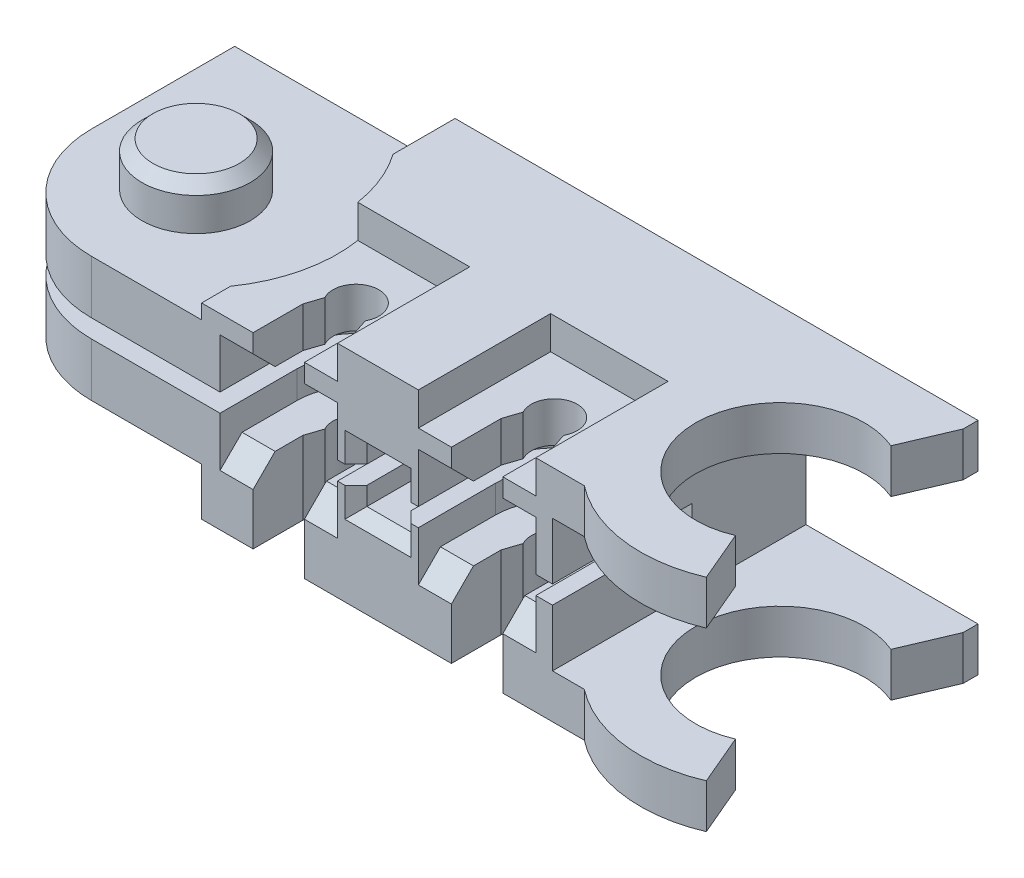
SolidWorks part; units mm, degrees
ref_plane "Front Plane" through (0, 0, 0) normal (0, 0, 1) x (1, 0, 0)
ref_plane "Top Plane" through (0, 0, 0) normal (0, 1, 0) x (1, 0, 0)
ref_plane "Right Plane" through (0, 0, 0) normal (1, 0, 0) x (0, 0, -1)
sketch "Sketch1" plane through (0, 0, 0) normal (0, 0, 1) x (1, 0, 0)
  line L0 (0, 0) -> (-17.5, 0) construction
  line L5 (-17.5, 0) -> (-35.5, 0) construction
  line L6 (-35.5, 0) -> (-53, 0) construction
  line L7 (-53, -5.67) -> (-45.5, -5.67) construction
  line L8 (-53, -10) -> (0, -10) construction
  line L9 (-53, -10) -> (-53, 10) construction
  line L10 (-53, 10) -> (0, 10) construction
  line L11 (0, -10) -> (0, 10) construction
  line L12 (-53, -10) -> (0, 10) construction
  line L13 (-53, 10) -> (0, -10) construction
  line L14 (-42.5, -10) -> (-42.5, -5.67)
  line L15 (-42.5, -5.67) -> (-53, -5.67)
  line L16 (-42.5, 10) -> (-42.5, 5.67)
  line L17 (-42.5, 5.67) -> (-53, 5.67)
  line L18 (-53, 5.67) -> (-62.5, 5.67)
  line L19 (-62.5, 5.67) -> (-62.5, -5.67)
  line L20 (-62.5, -5.67) -> (-53, -5.67)
  line L21 (-42.5, 10) -> (0, 10) construction
  line L22 (-42.5, -10) -> (0, -10)
  line L23 (0, 10) -> (3, 10)
  line L24 (3, 10) -> (3, 6)
  line L25 (3, 6) -> (0, 6)
  line L26 (0, -10) -> (3, -10)
  line L27 (3, -10) -> (3, -6)
  line L28 (3, -6) -> (0, -6)
  line L29 (0, 6) -> (0, -6) construction
  line L30 (0, 6) -> (-10.66, 6)
  line L31 (-10.66, 6) -> (-10.66, -6)
  line L32 (-10.66, -6) -> (0, -6)
  line L33 (-7.5, 0) -> (0, 0) construction
  line L34 (-7.5, 0) -> (-10.66, 0) construction
  line L35 (-42.5, 10) -> (0, 10)
  line L36 (0, 0) -> (3, 0) construction
  line L37 (3, 0) -> (3, 6) construction
  line L38 (-45.5, -5.67) -> (-42.5, -5.67) construction
  point P2 (-26.5, 0)
  dimension "D2" = 17.5
  dimension "D3" = 18
  dimension "D4" = 17.5
  dimension "D6" = 20
  dimension "D7" = 4.33
  dimension "D8" = 4
  dimension "D1" = 7.5
  dimension "D9" = 3
  dimension "D5" = 7.5
  dimension "D12" = 3
  dimension "D10" = 20
  dimension "D11" = 10.66
sketch "Sketch16" plane through (0, 0, 0) normal (0, 0, 1) x (1, 0, 0)
  line L18 (-42.5, -10) -> (0, -10)
  line L19 (0, -10) -> (3, -10)
  line L20 (3, -10) -> (3, -6)
  line L21 (3, -6) -> (0, -6)
  line L22 (0, -6) -> (-10.66, -6)
  line L23 (-10.66, -6) -> (-10.66, 6)
  line L24 (-10.66, 6) -> (0, 6)
  line L25 (0, 6) -> (3, 6)
  line L26 (3, 6) -> (3, 10)
  line L27 (3, 10) -> (0, 10)
  line L28 (0, 10) -> (-42.5, 10)
  line L29 (-42.5, 10) -> (-42.5, 5.67)
  line L30 (-42.5, 5.67) -> (-53, 5.67)
  line L31 (-53, 5.67) -> (-62.5, 5.67)
  line L32 (-62.5, 5.67) -> (-62.5, -5.67)
  line L33 (-62.5, -5.67) -> (-53, -5.67)
  line L34 (-53, -5.67) -> (-42.5, -5.67)
  line L35 (-42.5, -5.67) -> (-42.5, -10)
  line L36 (-42.5, -10) -> (0, -10)
  line L37 (0, -10) -> (3, -10)
  line L38 (3, -10) -> (3, -6)
  line L39 (3, -6) -> (0, -6)
  line L40 (0, -6) -> (-10.66, -6)
  line L41 (-10.66, -6) -> (-10.66, 6)
  line L42 (-10.66, 6) -> (0, 6)
  line L43 (0, 6) -> (3, 6)
  line L44 (3, 6) -> (3, 10)
  line L45 (3, 10) -> (0, 10)
  line L46 (0, 10) -> (-42.5, 10)
  line L47 (-42.5, 10) -> (-42.5, 5.67)
  line L48 (-42.5, 5.67) -> (-53, 5.67)
  line L49 (-53, 5.67) -> (-62.5, 5.67)
  line L50 (-62.5, 5.67) -> (-62.5, -5.67)
  line L51 (-62.5, -5.67) -> (-53, -5.67)
  line L52 (-53, -5.67) -> (-42.5, -5.67)
  line L53 (-42.5, -5.67) -> (-42.5, -10)
  dimension "D1" = 0
extrude "Boss-Extrude7" add sketch "Sketch16" along normal blind 20
sketch "Sketch2" plane through (0, -5.67, 0) normal (0, -1, 0) x (1, 0, 0)
  line L0 (-53, 0) -> (0, 0) construction
  line L1 (-53, 0) -> (0, 0) construction
  line L2 (-53, 0) -> (-53, 20) construction
  line L4 (-62.5, 20) -> (-42.5, 20) construction
  circle A0 centre (-53, 10) radius 4.9175
  dimension "D1" = 9.835
extrude "Boss-Extrude2" add sketch "Sketch2" along normal blind 4
sketch "Sketch3" plane through (0, -10, 0) normal (0, -1, 0) x (1, 0, 0)
  line L0 (0, 0) -> (0, 20) construction
  line L2 (-42.5, 20) -> (3, 20) construction
  circle A0 centre (0, 10) radius 7.665
  dimension "D1" = 15.33
extrude "Cut-Extrude1" cut sketch "Sketch3" against normal up to surface (20 mm away) up to face at (-19.75, 10, 10)
mirror "Mirror1" about plane through (0, 0, 0) normal (0, 1, 0) of "Boss-Extrude2"
sketch "Sketch4" plane through (0, 0, 20) normal (0, 0, 1) x (1, 0, 0)
  line L0 (0, -10) -> (0, 10) construction
  line L1 (0, -10) -> (0, 10) construction
  line L2 (0, 0) -> (-26.5, 0) construction
  line L3 (-17.5, 0) -> (-35.5, 0) construction
  line L4 (-28.5, 2.5) -> (-24.5, 2.5)
  line L5 (-28.5, -2.5) -> (-24.5, -2.5) construction
  line L6 (-28.5, -2.5) -> (-28.5, 2.5)
  line L7 (-28.5, 2.5) -> (-24.5, 2.5) construction
  line L8 (-24.5, -2.5) -> (-24.5, 2.5) construction
  line L9 (-28.5, -2.5) -> (-24.5, 2.5) construction
  line L10 (-28.5, 2.5) -> (-24.5, -2.5) construction
  line L11 (-28.5, -2.5) -> (-24.5, -2.5)
  line L12 (-24.5, 2.5) -> (-24.5, -2.5)
  dimension "D3" = 26.5
extrude "Cut-Extrude2" cut sketch "Sketch4" against normal blind 10
sketch "Sketch10" plane through (0, -10, 0) normal (0, -1, 0) x (1, 0, 0)
  line L0 (3, 17.0535) -> (4.9569, 21.6547)
  line L1 (4.9569, -1.6547) -> (3, 2.9465)
  arc A1 (3, 17.0535) -> (3, 2.9465) centre (0, 10) ccw
  arc A2 (4.9569, 21.6547) -> (4.9569, -1.6547) centre (0, 10) ccw
  arc A3 (3, 17.0535) -> (3, 2.9465) centre (0, 10) ccw construction
  dimension "D1" = 5
  dimension "D2" = 7.665
extrude "Boss-Extrude4" add sketch "Sketch10" against normal up to surface (4 mm away) up to face at (-3.3308, -6, 10)
sketch "Sketch11" plane through (0, 10, 0) normal (0, 1, 0) x (1, 0, 0)
  line L6 (4.9569, -21.6547) -> (3, -17.0535)
  line L8 (3, -2.9465) -> (4.9569, 1.6547)
  line L17 (-7.7719, 0) -> (-10.66, 0)
  line L19 (-10.66, 0) -> (-10.66, -20)
  line L20 (-10.66, -20) -> (-7.7719, -20)
  line L21 (4.9569, -21.6547) -> (3, -17.0535)
  line L22 (3, -2.9465) -> (4.9569, 1.6547)
  line L23 (-7.7719, 0) -> (-10.66, 0)
  line L24 (-10.66, 0) -> (-10.66, -20)
  line L25 (-10.66, -20) -> (-7.7719, -20)
  arc A11 (3, -2.9465) -> (3, -17.0535) centre (0, -10) ccw
  arc A12 (4.9569, 1.6547) -> (-7.7719, 0) centre (0, -10) ccw
  arc A13 (-7.7719, -20) -> (4.9569, -21.6547) centre (0, -10) ccw
  arc A14 (3, -2.9465) -> (3, -17.0535) centre (0, -10) ccw
  arc A15 (4.9569, 1.6547) -> (-7.7719, 0) centre (0, -10) ccw
  arc A16 (-7.7719, -20) -> (4.9569, -21.6547) centre (0, -10) ccw
  dimension "D1" = 0
extrude "Boss-Extrude5" add sketch "Sketch11" against normal up to surface (4 mm away) up to face at (-3.3308, 6, 10)
sketch "Sketch25" plane through (0, -10, 0) normal (0, -1, 0) x (1, 0, 0)
  circle A0 centre (-53, 10) radius 12.83
  circle A1 centre (-53, 10) radius 4.9175 construction
  circle A2 centre (-53, 10) radius 4.9175
  dimension "D1" = 25.66
extrude "Cut-Extrude9" cut sketch "Sketch25" against normal up to surface (4.33 mm away) up to face at (-57.9175, -5.67, 10)
sketch "Sketch26" plane through (0, 10, 0) normal (0, 1, 0) x (1, 0, 0)
  line L0 (-42.5, -2.6272) -> (-42.5, -17.3728)
  arc A0 (-42.5, -17.3728) -> (-42.5, -2.6272) centre (-53, -10) ccw construction
  arc A1 (-42.5, -17.3728) -> (-42.5, -2.6272) centre (-53, -10) ccw
extrude "Cut-Extrude10" cut sketch "Sketch26" against normal up to surface (4.33 mm away) up to face at (-48.0825, 5.67, 10)
sketch "Sketch13" plane through (0, -10, 0) normal (0, -1, 0) x (1, 0, 0)
  line L0 (-35.5, 0) -> (-35.5, 20) construction
  line L3 (-17.5, 0) -> (-17.5, 20) construction
  line L5 (-35.5, 13) -> (-17.5, 13) construction
  line L6 (-35.5, 8) -> (-17.5, 8) construction
  line L7 (-37.335, 13.9847) -> (-33.665, 13.9847) construction
  line L8 (-37.83, 15.4847) -> (-33.17, 15.4847) construction
  line L9 (-37.83, 15.4847) -> (-37.83, 20)
  line L10 (-37.83, 20) -> (-33.17, 20)
  line L11 (-33.17, 15.4847) -> (-33.17, 20)
  line L12 (-37.83, 15.4847) -> (-33.17, 20) construction
  line L13 (-37.83, 20) -> (-33.17, 15.4847) construction
  line L14 (-19.83, 15.4847) -> (-15.17, 15.4847) construction
  line L15 (-19.83, 15.4847) -> (-19.83, 20)
  line L16 (-19.83, 20) -> (-15.17, 20)
  line L17 (-15.17, 15.4847) -> (-15.17, 20)
  line L18 (-19.83, 15.4847) -> (-15.17, 20) construction
  line L19 (-19.83, 20) -> (-15.17, 15.4847) construction
  line L20 (-19.335, 13.9847) -> (-15.665, 13.9847) construction
  line L21 (-37.83, 15.4847) -> (-37.335, 13.9847)
  line L22 (-33.665, 13.9847) -> (-33.17, 15.4847)
  line L23 (-19.83, 15.4847) -> (-19.335, 13.9847)
  line L24 (-15.665, 13.9847) -> (-15.17, 15.4847)
  line L25 (-42.5, 20) -> (-7.7719, 20) construction
  line L26 (-42.5, 0) -> (-7.7719, 0) construction
  line L29 (-42.5, 0) -> (0, 0) construction
  line L30 (-17.5, 18) -> (-17.5, 20) construction
  circle A0 centre (-35.5, 13) radius 2.0825 construction
  circle A1 centre (-17.5, 13) radius 2.0825 construction
  circle A2 centre (-35.5, 13) radius 5 construction
  circle A3 centre (-17.5, 13) radius 5 construction
  arc A4 (-37.335, 13.9847) -> (-33.665, 13.9847) centre (-35.5, 13) ccw
  arc A5 (-19.335, 13.9847) -> (-15.665, 13.9847) centre (-17.5, 13) ccw
  point P11 (-35.5, 0)
  point P13 (-17.5, 0)
  point P22 (-35.5, 17.7423)
  point P27 (-17.5, 17.7423)
  point P46 (-17.5, 0)
  point P47 (-35.5, 0)
  dimension "D1" = 4.165
  dimension "D2" = 10
  dimension "D4" = 4.66
  dimension "D5" = 3.67
  dimension "D6" = 1.5
extrude "Cut-Extrude5" cut sketch "Sketch13" against normal through all
sketch "Sketch17" plane through (0, 0, 20) normal (0, 0, 1) x (1, 0, 0)
  line L1 (-40.83, -3.33) -> (-30.17, -3.33)
  line L2 (-40.83, -3.33) -> (-40.83, 3.33)
  line L3 (-40.83, 3.33) -> (-30.17, 3.33)
  line L4 (-30.17, -3.33) -> (-30.17, 3.33)
  line L5 (-40.83, -3.33) -> (-30.17, 3.33) construction
  line L6 (-40.83, 3.33) -> (-30.17, -3.33) construction
  line L7 (-22.83, -3.33) -> (-12.17, -3.33)
  line L8 (-22.83, -3.33) -> (-22.83, 3.33)
  line L9 (-22.83, 3.33) -> (-12.17, 3.33)
  line L10 (-12.17, -3.33) -> (-12.17, 3.33)
  line L11 (-22.83, -3.33) -> (-12.17, 3.33) construction
  line L12 (-22.83, 3.33) -> (-12.17, -3.33) construction
  point P0 (-35.5, 0)
  point P6 (-17.5, 0)
  dimension "D1" = 10.66
  dimension "D2" = 6.66
extrude "Cut-Extrude6" cut sketch "Sketch17" against normal blind 7
ref_axis "Axis1" through (-17.5, 10, 13) along (0, -1, 0)
ref_axis "Axis2" through (-35.5, 10, 13) along (0, -1, 0)
sketch "Sketch18" plane through (0, 0, 13) normal (0, 0, 1) x (1, 0, 0)
  line L4 (-37.5825, 3.33) -> (-40.83, 3.33)
  line L5 (-40.83, 3.33) -> (-40.83, -3.33)
  line L6 (-40.83, -3.33) -> (-37.5825, -3.33)
  line L7 (-37.5825, -3.33) -> (-37.5825, 3.33)
  line L8 (-37.5825, 3.33) -> (-40.83, 3.33)
  line L9 (-40.83, 3.33) -> (-40.83, -3.33)
  line L10 (-40.83, -3.33) -> (-37.5825, -3.33)
  line L12 (-37.5825, -3.33) -> (-37.5825, 3.33)
  dimension "D1" = 0
revolve "Cut-Revolve1" cut sketch "Sketch18" angle 360 about axis through (-35.5, 10, 13) along (0, -1, 0)
sketch "Sketch19" plane through (0, 0, 13) normal (0, 0, 1) x (1, 0, 0)
  line L4 (-19.5825, 3.33) -> (-22.83, 3.33)
  line L5 (-22.83, 3.33) -> (-22.83, -3.33)
  line L6 (-22.83, -3.33) -> (-19.5825, -3.33)
  line L7 (-19.5825, -3.33) -> (-19.5825, 3.33)
  line L8 (-19.5825, 3.33) -> (-22.83, 3.33)
  line L9 (-22.83, 3.33) -> (-22.83, -3.33)
  line L10 (-22.83, -3.33) -> (-19.5825, -3.33)
  line L12 (-19.5825, -3.33) -> (-19.5825, 3.33)
  dimension "D1" = 0
revolve "Cut-Revolve2" cut sketch "Sketch19" angle 360 about axis through (-17.5, 10, 13) along (0, -1, 0)
sketch "Sketch20" plane through (0, 0, 20) normal (0, 0, 1) x (1, 0, 0)
  line L0 (-62.5, 5.67) -> (-62.5, -5.67) construction
  line L1 (-62.5, 0.83) -> (-10.66, 0.83)
  line L2 (-62.5, 0.83) -> (-62.5, -0.83)
  line L3 (-62.5, -0.83) -> (-10.66, -0.83)
  line L4 (-10.66, 0.83) -> (-10.66, -0.83)
  line L5 (-10.66, 6) -> (-10.66, -6) construction
  dimension "D1" = 1.66
extrude "Cut-Extrude7" cut sketch "Sketch20" against normal blind 12.66
chamfer "Chamfer2" distance 1 angle 45 1 edges at (-48.0825, -9.67, 10)
chamfer "Chamfer3" distance 1 angle 45 1 edges at (-48.0825, 9.67, 10)
chamfer "Chamfer4" distance 2 angle 45 8 edges at (-21.33, 3.33, 20) (-21.33, -3.33, 20) (-13.67, -3.33, 20) (-13.67, 3.33, 20) (-39.33, -3.33, 20) (-39.33, 3.33, 20) (-31.67, -3.33, 20) (-31.67, 3.33, 20)
fillet "Fillet1" radius 10 3 edges at (-62.5, 0, 0) (-62.5, 3.25, 20) (-62.5, -3.25, 20)
ref_plane "Plane1" through (0, 0, -3) normal (0, 0, -1) x (-1, 0, 0)
sketch "Sketch22" plane through (0, 0, -3) normal (0, 0, -1) x (-1, 0, 0)
  line L0 (62.5, 5.67) -> (52.5, 5.67) construction
  line L1 (52.5, -5.67) -> (62.5, -5.67) construction
  line L2 (62.5, -5.67) -> (62.5, -0.83) construction
  line L3 (62.5, -0.83) -> (62.1397, -0.83) construction
  line L4 (62.1397, -0.83) -> (62.1397, 0.83) construction
  line L5 (62.1397, 0.83) -> (62.5, 0.83) construction
  line L6 (62.5, 0.83) -> (62.5, 5.67) construction
  line L7 (-4.9569, 6) -> (7.7719, 6) construction
  line L8 (7.7719, 10) -> (-4.9569, 10) construction
  line L9 (-4.9569, 10) -> (-4.9569, 6) construction
  line L10 (7.7719, -6) -> (-4.9569, -6) construction
  line L11 (-4.9569, -6) -> (-4.9569, -10) construction
  line L12 (-4.9569, -10) -> (7.7719, -10) construction
  line L13 (42.5, -5.67) -> (52.5, -5.67) construction
  line L14 (52.5, 5.67) -> (42.5, 5.67) construction
  line L15 (42.5, 5.67) -> (42.5, 10) construction
  line L16 (42.5, 10) -> (7.7719, 10) construction
  line L17 (7.7719, 6) -> (10.66, 6) construction
  line L18 (10.66, 6) -> (10.66, -6) construction
  line L19 (10.66, -6) -> (7.7719, -6) construction
  line L20 (7.7719, -10) -> (42.5, -10) construction
  line L21 (42.5, -10) -> (42.5, -5.67) construction
  line L22 (62.5, 5.67) -> (52.5, 5.67)
  line L23 (52.5, -5.67) -> (62.5, -5.67)
  line L24 (62.5, -5.67) -> (62.5, -0.83)
  line L25 (62.5, -0.83) -> (62.1397, -0.83)
  line L26 (62.1397, -0.83) -> (62.1397, 0.83)
  line L27 (62.1397, 0.83) -> (62.5, 0.83)
  line L28 (62.5, 0.83) -> (62.5, 5.67)
  line L29 (-4.9569, 6) -> (7.7719, 6)
  line L30 (7.7719, 10) -> (-4.9569, 10)
  line L31 (-4.9569, 10) -> (-4.9569, 6)
  line L32 (7.7719, -6) -> (-4.9569, -6)
  line L33 (-4.9569, -6) -> (-4.9569, -10)
  line L34 (-4.9569, -10) -> (7.7719, -10)
  line L35 (42.5, -5.67) -> (52.5, -5.67)
  line L36 (52.5, 5.67) -> (42.5, 5.67)
  line L37 (42.5, 5.67) -> (42.5, 10)
  line L38 (42.5, 10) -> (7.7719, 10)
  line L39 (7.7719, 6) -> (10.66, 6)
  line L40 (10.66, 6) -> (10.66, -6)
  line L41 (10.66, -6) -> (7.7719, -6)
  line L42 (7.7719, -10) -> (42.5, -10)
  line L43 (42.5, -10) -> (42.5, -5.67)
extrude "Boss-Extrude13" add sketch "Sketch22" against normal up to body
sketch "Sketch23" plane through (-62.1397, 0, 0) normal (-1, 0, 0) x (0, 0, 1)
  line L4 (-3, -0.83) -> (7.34, -0.83)
  line L5 (7.34, -0.83) -> (7.34, 0.83)
  line L6 (7.34, 0.83) -> (-3, 0.83)
  line L7 (-3, 0.83) -> (-3, -0.83)
  line L8 (-3, -0.83) -> (7.34, -0.83)
  line L9 (7.34, -0.83) -> (7.34, 0.83)
  line L10 (7.34, 0.83) -> (-3, 0.83)
  line L11 (-3, 0.83) -> (-3, -0.83)
  dimension "D1" = 0
extrude "Boss-Extrude14" add sketch "Sketch23" along normal up to surface (0.3603 mm away) up to face at (-62.5, 3.25, 3.5)
sketch "Sketch24" plane through (0, 10, 0) normal (0, 1, 0) x (1, 0, 0)
  line L0 (-37.83, -20) -> (-42.5, -20) construction
  line L1 (-42.5, -20) -> (-30.17, -20)
  line L2 (-42.5, -20) -> (-42.5, -8)
  line L3 (-42.5, -8) -> (-30.17, -8)
  line L4 (-30.17, -20) -> (-30.17, -8)
  line L5 (-19.83, -20) -> (-33.17, -20) construction
  line L6 (-22.83, -20) -> (-12.17, -20)
  line L7 (-22.83, -20) -> (-22.83, -8)
  line L8 (-22.83, -8) -> (-12.17, -8)
  line L9 (-12.17, -20) -> (-12.17, -8)
  line L11 (-33.17, -15.4847) -> (-33.17, -20) construction
  line L12 (-19.83, -20) -> (-19.83, -15.4847) construction
  line L13 (-15.17, -15.4847) -> (-15.17, -20) construction
  dimension "D2" = 3
  dimension "D3" = 3
  dimension "D4" = 3
  dimension "D5" = 12
extrude "Cut-Extrude8" cut sketch "Sketch24" against normal blind 3
chamfer "Chamfer5" distance 1 angle 45 6 edges at (-28.5, -1.665, 20) (-26.5, -2.5, 20) (-24.5, -1.665, 20) (-24.5, 1.665, 20) (-26.5, 2.5, 20) (-28.5, 1.665, 20)
ref_plane "Plane2" through (-19.75, 0, 19.75) normal (0.7071, 0, -0.7071) x (0, 1, 0)
ref_plane "Plane3" through (-6.83, 0, -6.83) normal (-0.7071, 0, -0.7071) x (0, -1, 0)
ref_plane "Plane4" through (-13.9011, 0, -13.9011) normal (-0.7071, 0, -0.7071) x (0, -1, 0)
ref_plane "Plane5" through (-16.2145, 0, 16.2145) normal (0.7071, 0, -0.7071) x (0, 1, 0)
sketch "Sketch27" plane through (-16.2145, 0, 16.2145) normal (0.7071, 0, -0.7071) x (0, 1, 0)
  line L0 (-10, -27.1734) -> (10, -27.1734)
  line L1 (-10, -27.1734) -> (10, -27.1734) construction
  line L2 (0, -29.2559) -> (0, -27.1734) construction
  circle A0 centre (0, -29.2559) radius 2.0825
  dimension "D1" = 4.165
extrude "Cut-Extrude11" cut sketch "Sketch27" against normal blind 14 and the other way blind 14
sketch "Sketch28" plane through (-13.9011, 0, -13.9011) normal (-0.7071, 0, -0.7071) x (0, -1, 0)
  line L0 (0, 13.3339) -> (0, 15.4164) construction
  line L2 (-10, 15.4164) -> (10, 15.4164) construction
  line L3 (-10, 15.4164) -> (10, 15.4164)
  line L4 (-10, 15.4164) -> (10, 15.4164) construction
  circle A0 centre (0, 13.3339) radius 2.0825
  dimension "D1" = 4.165
extrude "Cut-Extrude12" cut sketch "Sketch28" against normal blind 14
equation "\"offset\"=5"
equation "\"x_0\"=17.5"
equation "\"D2@Sketch1\"=\"x_0\""
equation "\"x_1\"=18"
equation "\"D3@Sketch1\"=\"x_1\""
equation "\"x_2\"=17.5"
equation "\"D4@Sketch1\"=\"x_2\""
equation "\"big_bearing_width\"=4"
equation "\"link_width\"= 20"
equation "\"link_height\"= 20"
equation "\"D6@Sketch1\"=\"link_width\""
equation "\"D7@Sketch1\"=\"big_bearing_width\"+\"tol\""
equation "\"D8@Sketch1\"=\"big_bearing_width\""
equation "\"D1@Boss-Extrude2\"=\"big_bearing_width\""
equation "\"big_bearing_OD\"=15"
equation "\"big_bearing_ID\"=10"
equation "\"D1@Sketch3\"=\"big_bearing_OD\"+\"tol\""
equation "\"D1@Sketch1\"=\"big_bearing_OD\"/2"
equation "\"big_bearing_offset\"=3"
equation "\"D9@Sketch1\"=\"big_bearing_offset\""
equation "\"D5@Sketch1\"=\"big_bearing_OD\"/2"
equation "\"D12@Sketch1\"=\"big_bearing_offset\""
equation "\"chuck_width\"=5"
equation "\"D4@Sketch4\"=\"chuck_width\""
equation "\"chuck_angle\"=0"
equation "\"D2@Sketch4\"=\"chuck_angle\""
equation "\"D1@Sketch4\"=\"chuck_angle\""
equation "\"chuck_length\"= 4"
equation "\"chuck_depth\"= 10"
equation "\"D1@Cut-Extrude2\"=\"chuck_depth\""
equation "\"D5@Sketch4\"=\"chuck_length\""
equation "\"chuck_distance\"=26.5"
equation "\"D3@Sketch4\"=\"chuck_distance\""
equation "\"post_width\"=4"
equation "\"post_length\"=6"
equation "\"small_bearing_width\"= 6"
equation "\"post_depth\"=10"
equation "\"pin_offset\"= 3"
equation "\"pin_dia\"=2"
equation "\"D1@Sketch2\"=\"big_bearing_ID\"-\"tol\"/2"
equation "\"tol\"= 0.33"
equation "\"big_bearing_backstop_offset\"=10"
equation "\"small_bearing_ID\"=4"
equation "\"small_bearing_OD\"=10"
equation "\"D1@Sketch13\"=\"small_bearing_ID\"+\"tol\"/2"
equation "\"D2@Sketch13\"=\"small_bearing_OD\""
equation "\"tendon_depth\"=12"
equation "\"D4@Sketch13\"=\"small_bearing_ID\"+2*\"tol\""
equation "\"press_transition_length\"=1.5"
equation "\"D6@Sketch13\"=\"press_transition_length\""
equation "\"D1@Boss-Extrude7\"=\"link_height\""
equation "\"D1@Sketch17\"=\"small_bearing_OD\"+2*\"tol\""
equation "\"D2@Sketch17\"=\"small_bearing_width\"+2*\"tol\""
equation "\"small_bearing_offset_from_top\"=2"
equation "\"D3@Sketch13\"=\"small_bearing_offset_from_top\""
equation "\"D1@Cut-Extrude6\"=\"small_bearing_offset_from_top\"+\"small_bearing_OD\"/2"
equation "\"tendon_dia\"=1"
equation "\"D1@Sketch20\"=\"tendon_dia\"+2*\"tol\""
equation "\"D1@Cut-Extrude7\"=\"small_bearing_offset_from_top\"+\"small_bearing_OD\"+2*\"tol\""
equation "\"D1@Sketch25\"=\"big_bearing_OD\"+10+2*\"tol\""
equation "\"front_tab_length\"=20"
equation "\"D10@Sketch1\"=\"front_tab_length\""
equation "\"D11@Sketch1\"=\"front_tab_length\"/2+2*\"tol\""
equation "\"D1@Sketch27\"=\"small_bearing_ID\"+\"tol\"/2"
equation "\"D1@Sketch28\"=\"small_bearing_ID\"+\"tol\"/2"
